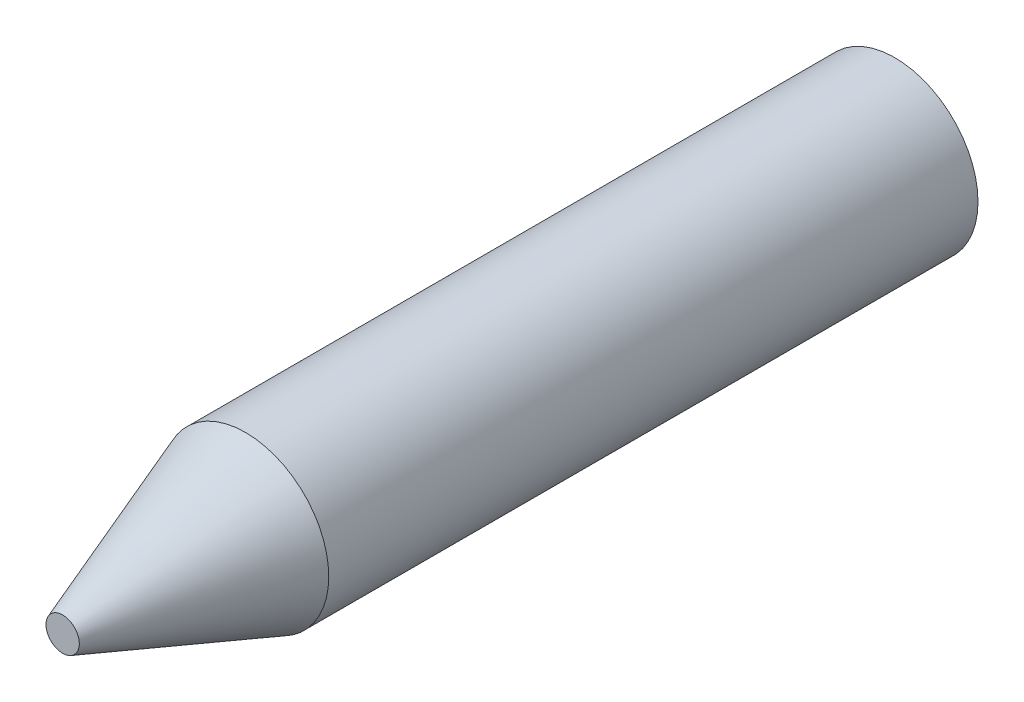
SolidWorks part; units mm, degrees
ref_plane "Front Plane" through (0, 0, 0) normal (0, 0, 1) x (1, 0, 0)
ref_plane "Top Plane" through (0, 0, 0) normal (0, 1, 0) x (1, 0, 0)
ref_plane "Right Plane" through (0, 0, 0) normal (1, 0, 0) x (0, 0, -1)
sketch "Sketch1" plane through (0, 0, 0) normal (0, 1, 0) x (1, 0, 0)
  line L0 (0, -68.6932) -> (0, 107.7398) construction
  line L1 (0, 100) -> (10, 100)
  line L2 (10, 100) -> (10, 21.9798)
  line L4 (0, 0) -> (0, 100)
  line L5 (10, 21.9798) -> (2, 0)
  line L6 (2, 0) -> (0, 0)
  dimension "D1" = 10
  dimension "D2" = 100
  dimension "D3" = 20
  dimension "D4" = 2
revolve "Revolve1" add sketch "Sketch1" angle 360 about L0
